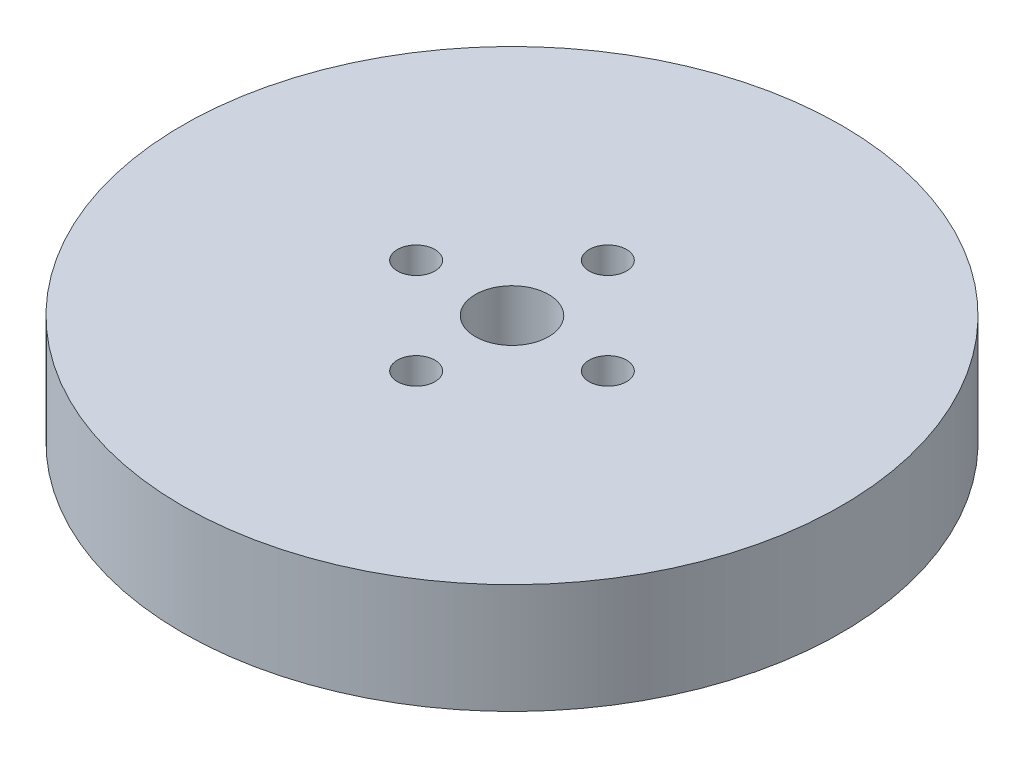
SolidWorks part; units mm, degrees
ref_plane "Front Plane" through (0, 0, 0) normal (0, 0, 1) x (1, 0, 0)
ref_plane "Top Plane" through (0, 0, 0) normal (0, 1, 0) x (1, 0, 0)
ref_plane "Right Plane" through (0, 0, 0) normal (1, 0, 0) x (0, 0, -1)
sketch "Sketch1" plane through (0, 0, 0) normal (0, 1, 0) x (1, 0, 0)
  circle A0 centre (0, 0) radius 90
  dimension "FLANGE_OD" = 180
extrude "Boss-Extrude1" add sketch "Sketch1" along normal blind 30
sketch "Sketch2" plane through (0, 0, 0) normal (0, 1, 0) x (1, 0, 0)
  circle A0 centre (0, 0) radius 10
  dimension "BORE_D" = 20
extrude "Cut-Extrude1" cut sketch "Sketch2" along normal through all
sketch "Sketch3" plane through (0, 30, 0) normal (0, 1, 0) x (1, 0, 0)
  circle A0 centre (0, 0) radius 26.1715 construction
  circle A1 centre (-26.1715, 0) radius 5.1191
  dimension "BOLT_D" = 10.2382
  dimension "BOLT_PCD" = 52.343
extrude "Cut-Extrude2" cut sketch "Sketch3" against normal blind 28.7859
pattern_circular "CirPattern1" count 4 over 360 about axis through (0, 0, 0) along (0, 1, 0) of "Cut-Extrude2"
